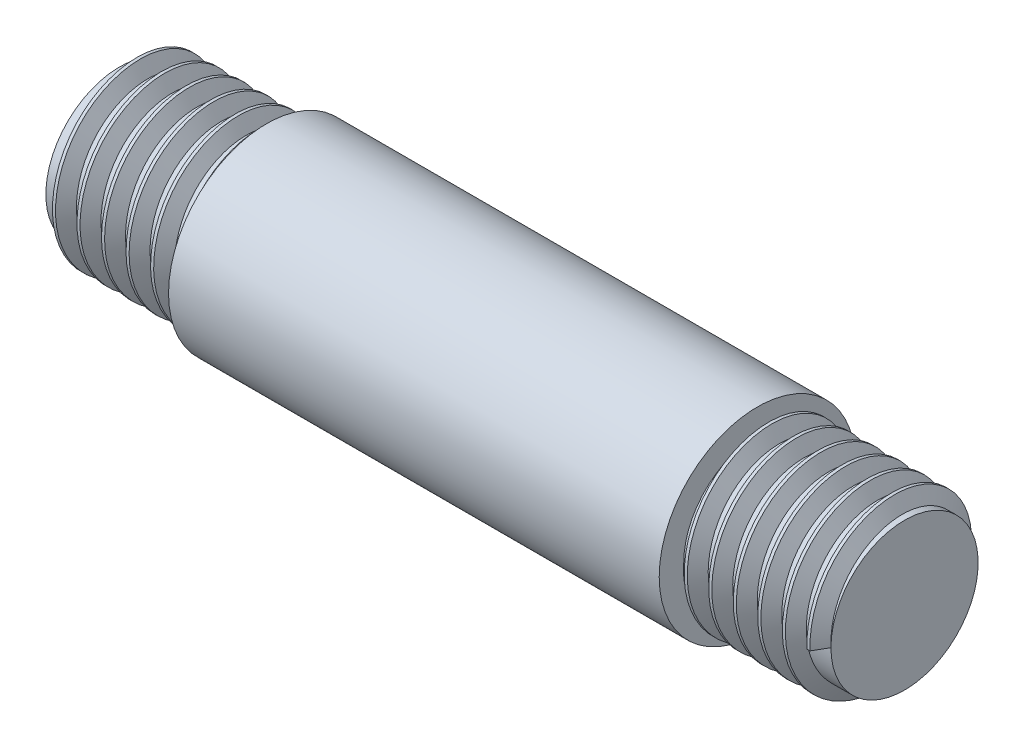
SolidWorks part; units mm, degrees
ref_plane "Front Plane" through (0, 0, 0) normal (0, 0, 1) x (1, 0, 0)
ref_plane "Top Plane" through (0, 0, 0) normal (0, 1, 0) x (1, 0, 0)
ref_plane "Right Plane" through (0, 0, 0) normal (1, 0, 0) x (0, 0, -1)
sketch "Sketch1" plane through (0, 0, 0) normal (0, 0, 1) x (1, 0, 0)
  line L0 (8, 0) -> (-8, 0)
  line L1 (-8, 0) -> (-8, 1.5)
  line L2 (-8, 1.5) -> (-5, 1.5)
  line L3 (-5, 1.5) -> (-5, 2)
  line L4 (-5, 2) -> (5, 2)
  line L5 (5, 2) -> (5, 1.5)
  line L6 (5, 1.5) -> (8, 1.5)
  line L7 (8, 1.5) -> (8, 0)
  point P4 (0, 0)
revolve "Revolve1" add sketch "Sketch1" angle 360 about L0
thread "Thread1" pitch 0.5 method extrude profile "Thread Profile1" start angle 0, offset 0, length 3, pitch 0.5, diameter 3
ref_plane "Plane1" through (8, 0, 1.5) normal (0, -1, 0) x (0, 0, 1)
sketch "Thread Profile1" plane through (8, 0, 1.5) normal (0, -1, 0) x (0, 0, 1)
  line L0 (0, 0) -> (0, 0.5) construction
  line L1 (0, 0) -> (0.2706, 0.1562)
  line L2 (0.2706, 0.1562) -> (0.2706, 0.2187)
  line L3 (0.2706, 0.2187) -> (0, 0.375)
  line L4 (0.2706, 0.1875) -> (0, 0.1875) construction
  line L11 (0, 0) -> (0, 0.375)
  point P2 (0, 0)
  dimension "Pitch" = 0.5
  dimension "Profile_Angle" = 60
  dimension "Profile_Land" = 0.0625
  dimension "Profile_Height" = 0.2706
thread "Thread2" pitch 0.5 method extrude profile "Thread Profile2" start angle 0, offset 0, length 3, pitch 0.5, diameter 3
ref_plane "Plane2" through (-8, 0, -1.5) normal (0, -1, 0) x (0, 0, -1)
sketch "Thread Profile2" plane through (-8, 0, -1.5) normal (0, -1, 0) x (0, 0, -1)
  line L0 (0, 0) -> (0, 0.5) construction
  line L1 (0, 0) -> (0.2706, 0.1562)
  line L2 (0.2706, 0.1562) -> (0.2706, 0.2187)
  line L3 (0.2706, 0.2187) -> (0, 0.375)
  line L4 (0.2706, 0.1875) -> (0, 0.1875) construction
  line L11 (0, 0) -> (0, 0.375)
  point P2 (0, 0)
  dimension "Pitch" = 0.5
  dimension "Profile_Angle" = 60
  dimension "Profile_Land" = 0.0625
  dimension "Profile_Height" = 0.2706
